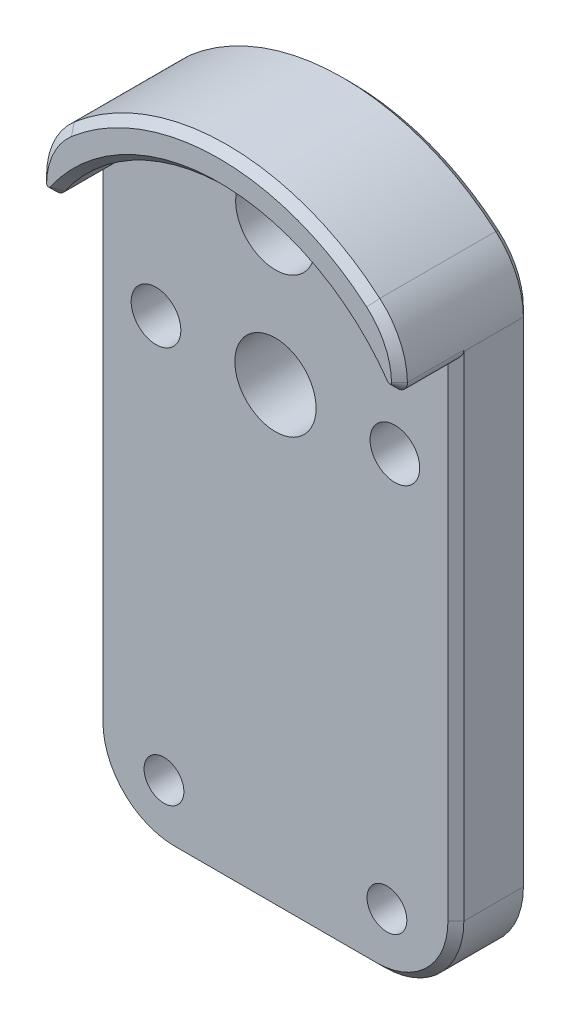
SolidWorks part; units mm, degrees
material "Onyx"
ref_plane "Front" through (0, 0, 0) normal (0, 0, 1) x (1, 0, 0)
ref_plane "Top" through (0, 0, 0) normal (0, 1, 0) x (1, 0, 0)
ref_plane "Right" through (0, 0, 0) normal (1, 0, 0) x (0, 0, -1)
sketch "Sketch2" plane through (0, 0, 0) normal (0, 0, 1) x (1, 0, 0)
  line L0 (0, 15.3416) -> (0, -36.5125) construction
  line L1 (14.3891, -36.5125) -> (-14.3891, -36.5125)
  line L2 (14.3891, -36.5125) -> (14.3891, 11.7424)
  line L4 (-14.3891, -36.5125) -> (-14.3891, 11.7424)
  line L5 (-15.4933, 0) -> (15.4933, 0) construction
  line L6 (-14.3891, 15.3416) -> (14.3891, 15.3416) construction
  line L8 (-14.3891, -28.0416) -> (14.3891, -28.0416) construction
  line L9 (-14.3891, -31.8516) -> (14.3891, -31.8516) construction
  line L10 (-8.89, 15.3416) -> (-8.89, -31.8516) construction
  line L11 (8.89, 15.3416) -> (8.89, -31.8516) construction
  circle A1 centre (0, 0) radius 3.2385
  arc A2 (-15.4933, 0) -> (15.4933, 0) centre (0, -0.1524) cw construction
  arc A7 (-14.3891, 11.7424) -> (14.3891, 11.7424) centre (0, -0.1524) cw
  arc A8 (-18.6681, 0.0312) -> (18.6681, 0.0312) centre (0, -0.1524) cw construction
  point P10 (0, 0)
  dimension "D4" = 6.477
  dimension "D2" = 15.494
  dimension "D1" = 28.7782
  dimension "D3" = 15.3416
  dimension "D8" = 5.4991
  dimension "D9" = 5.4991
  dimension "D5" = 43.3832
  dimension "D11" = 3.81
  dimension "D12" = 4.6609
  dimension "D6" = 3.175
extrude "Boss-Extrude1" add sketch "Sketch2" along normal blind 6.0198
sketch "Sketch12" plane through (0, 0, 6.0198) normal (0, 0, 1) x (1, 0, 0)
  line L2 (-14.3891, 6.2471) -> (-14.3891, 11.7424)
  line L3 (14.3891, 11.7424) -> (14.3891, 6.2471)
  arc A0 (15.4933, 0) -> (-15.4933, 0) centre (0, -0.1524) ccw construction
  arc A1 (15.4933, 0) -> (-15.4933, 0) centre (0, -0.1524) ccw construction
  arc A3 (-14.3891, 11.7424) -> (14.3891, 11.7424) centre (0, -0.1524) cw
  arc A4 (14.3891, 11.7424) -> (-14.3891, 11.7424) centre (0, -0.1524) ccw construction
  arc A5 (-14.3891, 6.2471) -> (14.3891, 6.2471) centre (0, -0.1524) cw
  dimension "D1" = 0.254
extrude "Boss-Extrude5" add sketch "Sketch12" along normal blind 4.4958
sketch "Sketch5" plane through (0, 0, 6.0198) normal (0, 0, 1) x (1, 0, 0)
  line L0 (-10.4775, 15.2993) -> (-10.4775, -36.5125) construction
  line L2 (-14.3891, -36.5125) -> (14.3891, -36.5125) construction
  line L3 (10.4775, 15.2993) -> (10.4775, -36.5125) construction
  line L4 (-10.4775, -10.6066) -> (10.4775, -10.6066) construction
  line L5 (0, 0) -> (0, -10.6066) construction
  circle A0 centre (-10.4775, -15.748) radius 1.9812 construction
  circle A1 centre (10.4775, -15.748) radius 1.9812 construction
  circle A2 centre (0, 0) radius 9.525 construction
  circle A3 centre (-9.525, 0) radius 1.9812
  circle A4 centre (9.525, 0) radius 1.9812
  arc A5 (14.3891, -12.0472) -> (-14.3891, -12.0472) centre (0, -0.1524) ccw construction
  dimension "D2" = 3.9624
  dimension "D3" = 19.05
  dimension "D1" = 20.955
  dimension "D5" = 15.748
extrude "Cut-Extrude2_EncoderScrewHoles" cut sketch "Sketch5" against normal through all
sketch "Sketch11" plane through (0, 0, 0) normal (0, 0, -1) x (-1, 0, 0)
  line L0 (14.3891, 11.7424) -> (14.3891, -36.5125) construction
  line L1 (9.525, -3.3729) -> (12.446, -1.6864)
  line L2 (12.446, -1.6864) -> (12.446, 1.6864)
  line L3 (12.446, 1.6864) -> (9.525, 3.3729)
  line L4 (9.525, 3.3729) -> (6.604, 1.6864)
  line L5 (6.604, 1.6864) -> (6.604, -1.6864)
  line L6 (6.604, -1.6864) -> (9.525, -3.3729)
  line L7 (-14.3891, -36.5125) -> (-14.3891, 11.7424) construction
  line L8 (-6.604, -1.6864) -> (-6.604, 1.6864)
  line L9 (-6.604, 1.6864) -> (-9.525, 3.3729)
  line L10 (-9.525, 3.3729) -> (-12.446, 1.6864)
  line L11 (-12.446, 1.6864) -> (-12.446, -1.6864)
  line L12 (-12.446, -1.6864) -> (-9.525, -3.3729)
  line L13 (-9.525, -3.3729) -> (-6.604, -1.6864)
  circle A0 centre (9.525, 0) radius 2.921 construction
  circle A1 centre (-9.525, 0) radius 2.921 construction
  circle A3 centre (-9.525, 0) radius 1.9812 construction
  dimension "D1" = 5.842
extrude "Cut-Extrude4" cut sketch "Sketch11" against normal blind 2.8448
sketch "Sketch13" plane through (0, 0, 6.0198) normal (0, 0, 1) x (1, 0, 0)
  line L0 (0, 0) -> (0, -36.5125) construction
  line L1 (-14.3891, -36.5125) -> (14.3891, -36.5125) construction
  line L2 (8.89, -31.75) -> (-8.89, -31.75) construction
  circle A1 centre (8.89, -31.75) radius 1.5875
  circle A2 centre (-8.89, -31.75) radius 1.5875
  point P9 (0, -31.75)
  dimension "D1" = 3.175
  dimension "D3" = 8.89
  dimension "D2" = 4.7625
extrude "Cut-Extrude5" cut sketch "Sketch13" against normal through all
ref_axis "Axis1" through (0, 0, 36.0066) along (0, 0, -1)
sketch "Sketch7" plane through (0, 0, 0) normal (0, 0, -1) x (-1, 0, 0)
  line L0 (0, 18.5166) -> (0, -36.5125) construction
  line L2 (14.3891, -36.5125) -> (-14.3891, -36.5125) construction
  line L3 (-14.3891, -15.875) -> (14.3891, -15.875) construction
  line L4 (14.3891, 6.2471) -> (14.3891, -36.5125) construction
  circle A0 centre (0, -15.875) radius 3.9688
  arc A1 (14.3891, -12.0472) -> (-14.3891, -12.0472) centre (0, -0.1524) ccw construction
  dimension "D1" = 7.9375
  dimension "D2" = 15.875
sketch "Sketch14" plane through (0, 0, 0) normal (0, 0, -1) x (-1, 0, 0)
  line L0 (0, 0) -> (0, 18.5166) construction
  arc A0 (14.3891, 11.7424) -> (-14.3891, 11.7424) centre (0, -0.1524) ccw construction
  circle A1 centre (0, 11.1125) radius 3.175
  dimension "D1" = 6.35
  dimension "D2" = 11.1125
extrude "Cut-Extrude6" cut sketch "Sketch14" against normal through all
fillet "Fillet1_0.25" radius 6.35 4 edges at (-14.3891, -36.5125, 3.0099) (14.3891, -36.5125, 3.0099) (14.3891, 11.7424, 5.2578) (-14.3891, 11.7424, 5.2578)
fillet "Fillet2_1/32" radius 0.7937 2 edges at (14.3891, 6.2471, 8.2677) (-14.3891, 6.2471, 8.2677)
fillet "Fillet4_1/128" radius 0.1984 24 edges at (12.446, -1.6864, 1.4224) (9.525, -3.3729, 1.4224) (6.604, -1.6864, 1.4224) (6.604, 1.6864, 1.4224) (9.525, 3.3729, 1.4224) (12.446, 1.6864, 1.4224) (12.446, 0, 2.8448) (10.9855, -2.5297, 2.8448) (8.0645, -2.5297, 2.8448) (6.604, 0, 2.8448) (8.0645, 2.5297, 2.8448) (10.9855, 2.5297, 2.8448) (-12.446, 1.6864, 1.4224) (-9.525, 3.3729, 1.4224) (-6.604, 1.6864, 1.4224) (-6.604, -1.6864, 1.4224) (-9.525, -3.3729, 1.4224) (-12.446, -1.6864, 1.4224) (-12.446, 0, 2.8448) (-10.9855, -2.5297, 2.8448) (-8.0645, -2.5297, 2.8448) (-6.604, 0, 2.8448) (-8.0645, 2.5297, 2.8448) (-10.9855, 2.5297, 2.8448)
chamfer "Chamfer1_0.25" distance 0.635 angle 45 21 edges at (12.5292, -34.6526, 6.0198) (14.3891, -10.4903, 6.0198) (-12.5292, -34.6526, 6.0198) (14.3889, 9.2333, 6.0198) (-14.3891, -10.4903, 6.0198) (-14.3889, 9.2333, 6.0198) (12.5292, -34.6526, 0) (-12.5292, -34.6526, 0) (14.3891, -10.4903, 0) (-14.3891, -10.4903, 0) (13.8113, 11.8286, 0) (-13.8113, 11.8286, 0) (0, 18.5166, 0) (0, -36.5125, 0) (0, -36.5125, 6.0198) (13.7897, 11.8752, 10.5156) (0, 18.5166, 10.5156) (-13.7897, 11.8752, 10.5156) (13.8376, 8.5162, 10.5156) (0, 15.5956, 10.5156) (-13.8376, 8.5162, 10.5156)
equation "\"D1@Boss-Extrude5\"=0.354/2"
equation "\"D2@Sketch7\"=1.25/2"
equation "\"D11@Sketch2\"=0.15000000"
equation "\"D12@Sketch2\"=0.1210000+0.0625"
